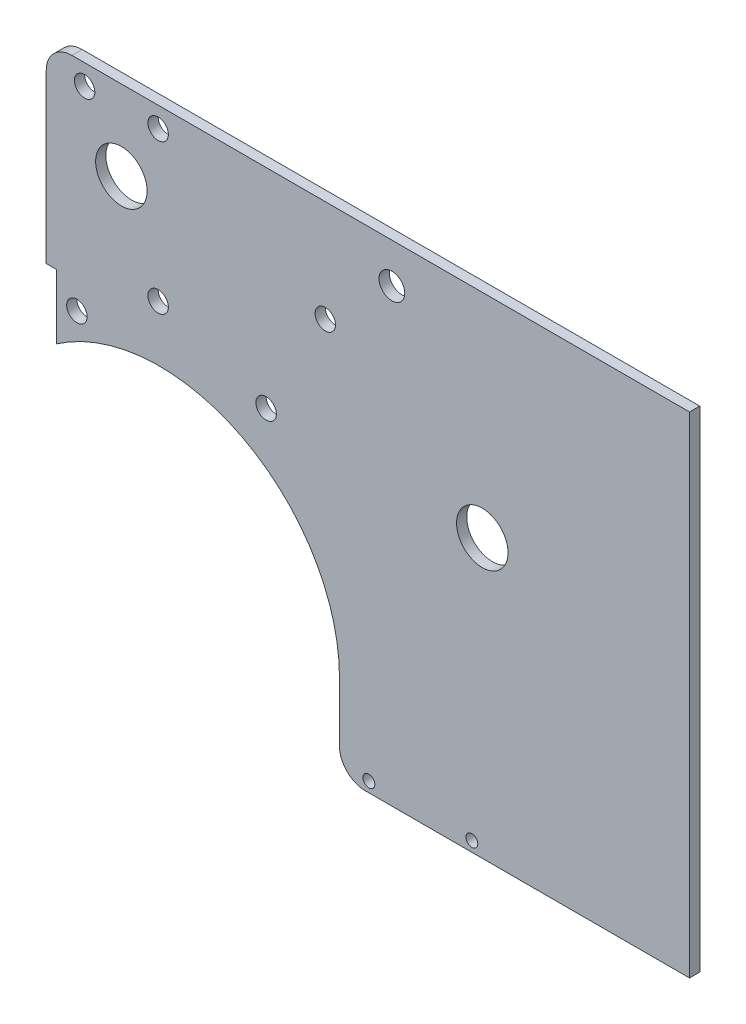
SolidWorks part; units mm, degrees
material "6061-T6 (SS)"
ref_plane "Front" through (0, 0, 0) normal (0, 0, 1) x (1, 0, 0)
ref_plane "Top" through (0, 0, 0) normal (0, 1, 0) x (1, 0, 0)
ref_plane "Right" through (0, 0, 0) normal (1, 0, 0) x (0, 0, -1)
ref_axis "side-side" through (80.9, 0, 0) along (-1, 0, 0)
ref_axis "up-down" through (0, 50, 0) along (0, -1, 0)
ref_axis "front-back" through (0, 0, -80.9) along (0, 0, 1)
sketch "Sketch2" plane through (0, 0, 0) normal (0, 0, 1) x (1, 0, 0)
  line L0 (0, 0) -> (0, 38.614) construction
  line L1 (32.608, -18.6739) -> (343.0334, 198.6883) construction
  line L2 (80.805, -4.0956) -> (40.4445, 15.3761) construction
  line L3 (55.8965, -12.0571) -> (64.2032, -15.9306) construction
  line L4 (64.2032, -15.9306) -> (71.7111, -10.6735) construction
  line L5 (71.7111, -10.6735) -> (70.9123, -1.5429) construction
  line L6 (70.9123, -1.5429) -> (62.6056, 2.3306) construction
  line L7 (62.6056, 2.3306) -> (55.0977, -2.9265) construction
  line L8 (55.0977, -2.9265) -> (55.8965, -12.0571) construction
  line L9 (50, 0) -> (-50, 0) construction
  line L10 (37.0625, -44.5827) -> (45, -49.1654) construction
  line L11 (45, -49.1654) -> (52.9375, -44.5827) construction
  line L12 (52.9375, -44.5827) -> (52.9375, -35.4173) construction
  line L13 (52.9375, -35.4173) -> (45, -30.8346) construction
  line L14 (45, -30.8346) -> (37.0625, -35.4173) construction
  line L15 (37.0625, -35.4173) -> (37.0625, -44.5827) construction
  line L16 (0, -50) -> (0, 50) construction
  line L18 (-20.1841, -46.8662) -> (-13.8341, -50.5323) construction
  line L19 (-13.8341, -50.5323) -> (-7.4841, -46.8662) construction
  line L20 (-7.4841, -46.8662) -> (-7.4841, -39.5338) construction
  line L21 (-7.4841, -39.5338) -> (-13.8341, -35.8677) construction
  line L22 (-13.8341, -35.8677) -> (-20.1841, -39.5338) construction
  line L23 (-20.1841, -39.5338) -> (-20.1841, -46.8662) construction
  line L25 (-20.1841, -57.2) -> (-20.1841, -35.2)
  line L26 (-23.3591, -57.2) -> (-20.1841, -57.2)
  line L27 (-23.3591, -35.2) -> (-23.3591, -57.2)
  line L28 (-20.1841, -35.2) -> (-23.3591, -35.2)
  line L29 (73.9, -121.2) -> (73.9, -127.55)
  line L30 (112, -121.2) -> (73.9, -121.2)
  line L31 (112, -127.55) -> (112, -121.2)
  line L32 (73.9, -127.55) -> (112, -127.55)
  circle A0 centre (63.4044, -6.8) radius 7.9375 construction
  circle A1 centre (63.4044, -6.8) radius 3.175
  circle A2 centre (45, -40) radius 7.9375 construction
  circle A3 centre (45, -40) radius 3.175
  circle A4 centre (-13.8341, -43.2) radius 6.35 construction
  circle A6 centre (84.1028, 12.5) radius 4
  circle A9 centre (-13.8341, -43.2) radius 3.175
  circle A10 centre (11.43, -27.96) radius 3.175
  circle A11 centre (-11.43, 18.5) radius 3.175
  circle A12 centre (11.43, 18.5) radius 3.175
  point P42 (0, 0)
  point P46 (63.3945, -6.807)
  dimension "D2" = 6.35
  dimension "D1" = 15.875
  dimension "D3" = 40
  dimension "D4" = 45
  dimension "D5" = 12.7
  dimension "D6" = 8
  dimension "D7" = 25.755
  dimension "D8" = 6.8
  dimension "D9" = 31.4225
sketch "Sketch1" plane through (0, 0, 0) normal (0, 0, 1) x (1, 0, 0)
  line L0 (-20.1841, -57.2) -> (-20.1841, -35.2) construction
  line L1 (176.6409, -127.55) -> (67.8159, -127.55)
  line L2 (176.6409, -127.55) -> (176.6409, 24.85)
  line L3 (176.6409, 24.85) -> (-23.3591, 24.85)
  line L4 (-23.3591, -35.2) -> (-23.3591, 24.85)
  line L5 (-20.1841, -35.2) -> (-23.3591, -35.2) construction
  line L6 (-20.1841, -55.2435) -> (-20.1841, -35.2)
  line L7 (-20.1841, -35.2) -> (-23.3591, -35.2)
  line L8 (-23.3591, -35.2) -> (-23.3591, -57.2) construction
  line L9 (73.9, -127.55) -> (112, -127.55) construction
  line L10 (67.8159, -101.2) -> (67.8159, -127.55)
  line L11 (108.95, -124.375) -> (112, -124.375) construction
  line L12 (112, -127.55) -> (112, -121.2) construction
  line L13 (76.95, -124.375) -> (73.9, -124.375) construction
  line L14 (73.9, -121.2) -> (73.9, -127.55) construction
  circle A0 centre (11.43, 18.5) radius 3.175 construction
  circle A1 centre (112.2, -41.275) radius 8
  circle A2 centre (-11.43, 18.5) radius 3.175 construction
  circle A3 centre (0, 0) radius 8
  circle A4 centre (11.43, -27.96) radius 3.175 construction
  circle A5 centre (11.43, -27.96) radius 3.175
  circle A6 centre (45, -40) radius 3.175 construction
  arc A7 (67.8159, -101.2) -> (-20.1841, -55.2435) centre (11.8159, -101.2) ccw
  circle A8 centre (-11.43, 18.5) radius 3.175
  circle A9 centre (11.43, 18.5) radius 3.175
  circle A10 centre (84.1028, 12.5) radius 4 construction
  circle A11 centre (63.4044, -6.8) radius 3.175 construction
  circle A12 centre (45, -40) radius 3.175
  circle A13 centre (63.4044, -6.8) radius 3.175
  circle A14 centre (108.95, -124.375) radius 1.85
  circle A15 centre (76.95, -124.375) radius 1.85
  circle A16 centre (-13.8341, -43.2) radius 3.175
  circle A17 centre (84.1028, 12.5) radius 4
  dimension "D4" = 24.85
  dimension "D5" = 16
  dimension "D6" = 112.2
  dimension "D7" = 41.275
  dimension "D1" = 56
  dimension "D3" = 3.7
  dimension "D9" = 32
  dimension "D2" = 23.3591
  dimension "D8" = 200
  dimension "D10" = 152.4
extrude "Boss-Extrude1" add sketch "Sketch1" against normal blind 3.175
fillet "Fillet1" radius 8 1 edges at (67.8159, -127.55, -1.5875)
fillet "Fillet2" radius 8 1 edges at (-23.3591, 24.85, -1.5875)
